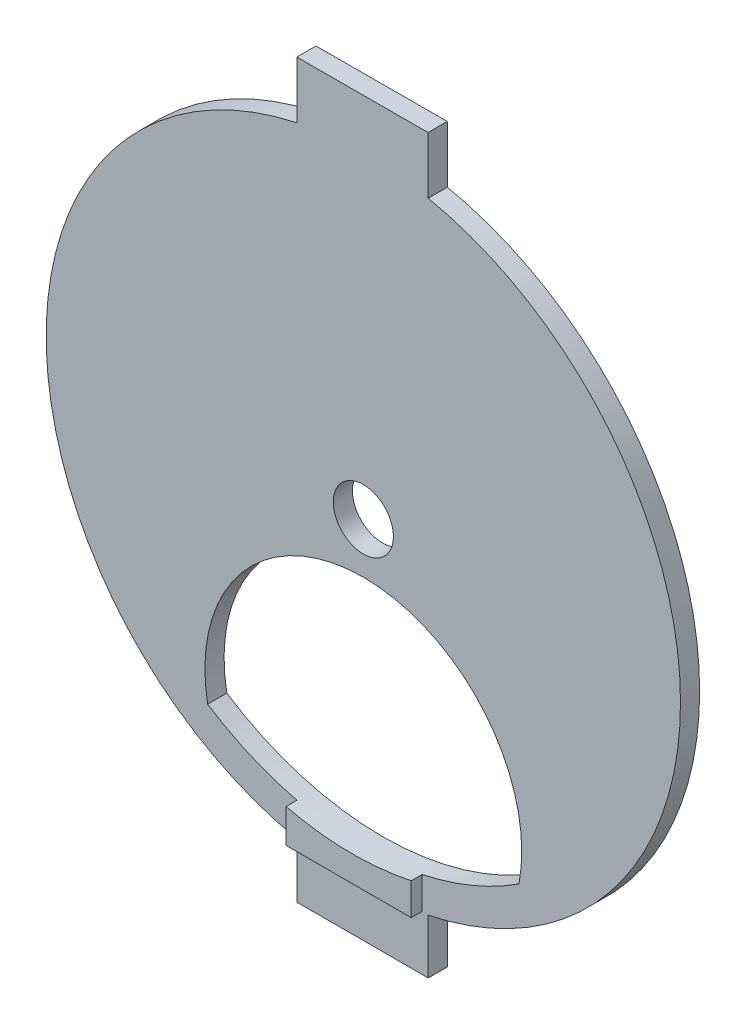
SolidWorks part; units mm, degrees
ref_plane "Front Plane" through (0, 0, 0) normal (0, 0, 1) x (1, 0, 0)
ref_plane "Top Plane" through (0, 0, 0) normal (0, 1, 0) x (1, 0, 0)
ref_plane "Right Plane" through (0, 0, 0) normal (1, 0, 0) x (0, 0, -1)
sketch "Sketch1" plane through (0, 0, 0) normal (0, 0, 1) x (1, 0, 0)
  line L0 (-38.5209, 180.076) -> (37.6791, 180.254)
  line L1 (-38.5209, 180.076) -> (-38.598, 213.096)
  line L2 (37.6791, 180.254) -> (37.602, 213.274)
  line L3 (-38.598, 213.096) -> (37.602, 213.274)
  line L4 (-38.5209, -180.076) -> (-38.5209, -211.826)
  line L5 (-38.5209, -180.076) -> (37.6791, -180.076)
  line L6 (-38.5209, -211.826) -> (37.6791, -211.826)
  line L7 (37.6791, -180.076) -> (37.6791, -211.826)
  circle A0 centre (0, 0) radius 184.15
  point P3 (-40.1146, 211.4777)
  point P10 (0, 0)
  point P13 (0, 0)
  point P14 (-39.3174, 212.1687)
  point P15 (37.5303, 211.7941)
  point P16 (0, 0)
  dimension "D1" = 368.3
  dimension "D2" = 33.02
  dimension "D3" = 76.2
  dimension "D4" = 76.2
  dimension "D5" = 31.75
extrude "Boss-Extrude1" add sketch "Sketch1" along normal blind 11.1252 contours A0 L2 L3 L1 | L0 A0 L5 L7 | A0 L4 L6 L7 | L0 L1 L3 L2 | L4 L5 L7 L6 region at (-0.4625, 197.9829, 0) region at (0.0008, 0.0115, 0) region at (-0.4595, -197.3023, 0)
sketch "Sketch5" plane through (0, 0, 11.1252) normal (0, 0, 1) x (1, 0, 0)
  circle A0 centre (0, 0) radius 17.4625
  dimension "D1" = 34.925
extrude "Cut-Extrude1" cut sketch "Sketch5" against normal blind 12.7
sketch "Sketch6" plane through (0, 0, 11.1252) normal (0, 0, 1) x (1, 0, 0)
  circle A0 centre (0, 0) radius 165.1
  arc A1 (-90.3753, -138.1677) -> (90.3753, -138.1677) centre (0, -121.0993) cw
  dimension "D1" = 330.2
extrude "Cut-Extrude4" cut sketch "Sketch6" against normal blind 12.7 contours A1 A0 region at (0, -100.8112, 11.1252)
sketch "Sketch7" plane through (0, 0, 11.1252) normal (0, 0, 1) x (1, 0, 0)
  line L0 (-38.5209, -180.076) -> (34.15, -180.076)
  line L1 (-38.5209, -180.076) -> (-38.5209, -160.297)
  line L2 (34.15, -180.076) -> (34.15, -160.297)
  line L3 (-38.5209, -160.297) -> (34.15, -160.297)
  arc M10 (90.3753, -138.1677) -> (-90.3753, -138.1677) centre (0, 0) cw
extrude "Boss-Extrude2" add sketch "Sketch7" along normal blind 6.35 contours L3 L1 L0 L2 M10 region at (-2.5475, -171.8624, 11.1252)
